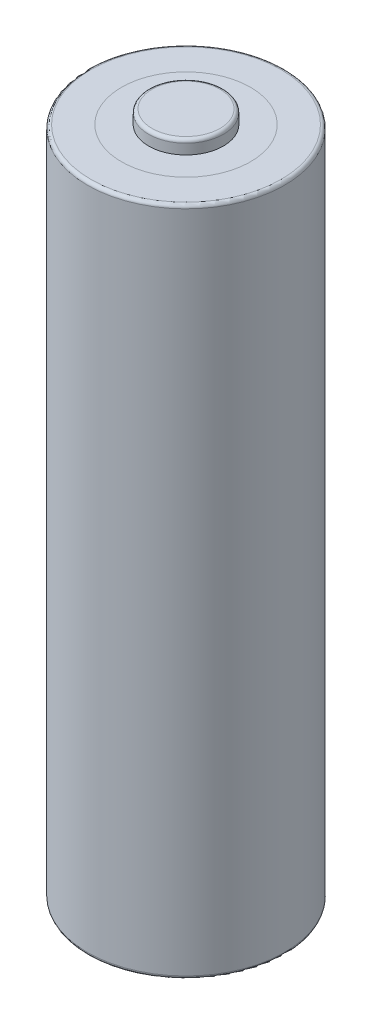
SolidWorks part; units mm, degrees
ref_plane "Front XY Plane" through (0, 0, 0) normal (0, 0, 1) x (1, 0, 0)
ref_plane "Top XZ Plane" through (0, 0, 0) normal (0, 1, 0) x (1, 0, 0)
ref_plane "Right ZY Plane" through (0, 0, 0) normal (1, 0, 0) x (0, 0, -1)
ref_axis "X Axix With Top and Front Plane" through (80.1915, 0, 0) along (-1, 0, 0)
ref_axis "Y Axix With Front and Right" through (0, -47.2301, 0) along (0, 1, 0)
ref_axis "Z Axix With Top and Right Plane" through (0, 0, -48.5416) along (0, 0, 1)
sketch "Sketch1" plane through (0, 0, 0) normal (0, 1, 0) x (1, 0, 0)
  circle A0 centre (0, 0) radius 7.25
  dimension "D1" = 14.5
sketch "Sketch2" plane through (0, 0, 0) normal (1, 0, 0) x (0, 0, -1)
  line L0 (0, 0) -> (0, 50.5)
  line L1 (0, 50.5) -> (2.5, 50.5)
  line L2 (2.75, 50.25) -> (2.75, 49.5)
  line L3 (2.75, 49.5) -> (7, 49.5)
  line L4 (7.25, 49.25) -> (7.25, 0.35)
  line L5 (7, 0.1) -> (3.5, 0.1)
  line L6 (3.5, 0.1) -> (3, 0)
  line L7 (3, 0) -> (0, 0)
  line L8 (0, 0) -> (0, -2.5805) construction
  arc A0 (7.25, 0.35) -> (7, 0.1) centre (7, 0.35) cw
  arc A1 (7, 49.5) -> (7.25, 49.25) centre (7, 49.25) cw
  arc A2 (2.5, 50.5) -> (2.75, 50.25) centre (2.5, 50.25) cw
  dimension "D8" = 0.25
  dimension "D1" = 7
  dimension "D2" = 0.1
  dimension "D3" = 0.5
  dimension "D4" = 14.5
  dimension "D5" = 5.5
  dimension "D6" = 1
  dimension "D7" = 50.5
revolve "Revolve1" add sketch "Sketch2" angle 360 about L8
sketch "Sketch3" plane through (0, 49.5, 0) normal (0, 1, 0) x (1, 0, 0)
  circle A2 centre (0, 0) radius 4.75
  circle A3 centre (0, 0) radius 4.75
  dimension "D1" = 2
split line "Split Line1"
